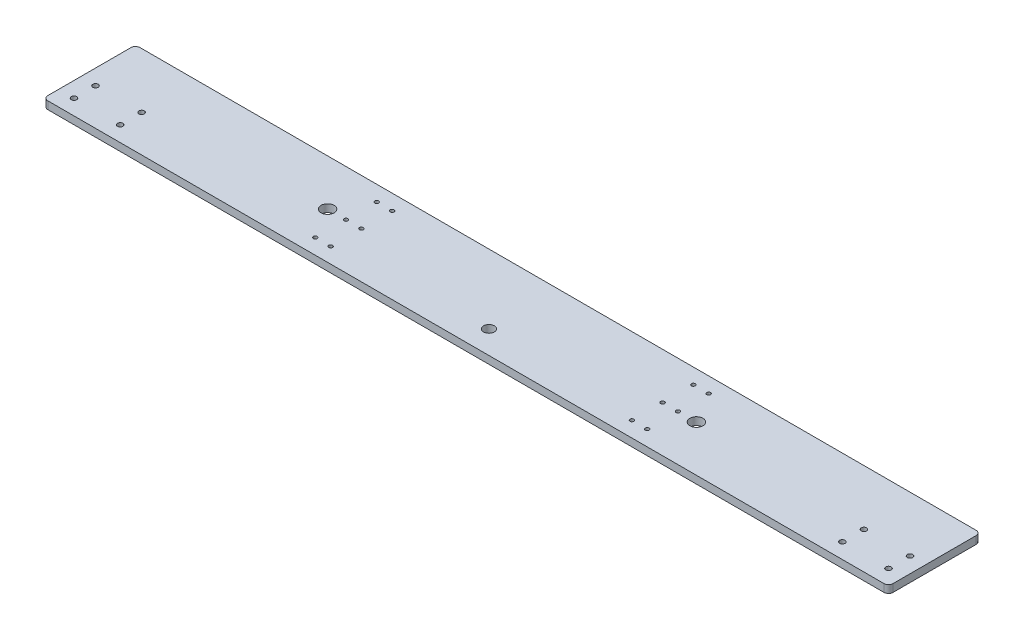
SolidWorks part; units mm, degrees
ref_plane "Front" through (0, 0, 0) normal (0, 0, 1) x (1, 0, 0)
ref_plane "Top" through (0, 0, 0) normal (0, 1, 0) x (1, 0, 0)
ref_plane "Right" through (0, 0, 0) normal (1, 0, 0) x (0, 0, -1)
sketch "草图1" plane through (0, 0, 0) normal (0, 1, 0) x (1, 0, 0)
  line L1 (-275, -30) -> (275, -30)
  line L2 (-275, -30) -> (-275, 30)
  line L3 (-275, 30) -> (275, 30)
  line L4 (275, -30) -> (275, 30)
  line L5 (-275, -30) -> (275, 30) construction
  line L6 (-275, 30) -> (275, -30) construction
  point P0 (0, 0)
  dimension "D1" = 550
  dimension "D2" = 60
extrude "凸台-拉伸1" add sketch "草图1" against normal blind 5 contours L3 L4 L1 L2
sketch "草图2" plane through (0, 0, 0) normal (0, 1, 0) x (1, 0, 0)
  line L0 (-275, -30) -> (275, -30) construction
  circle A0 centre (0, -15) radius 3.5
  dimension "D1" = 7
  dimension "D2" = 15
extrude "切除-拉伸2" cut sketch "草图2" against normal through all contours A0
sketch "草图4" plane through (0, 0, 0) normal (0, 1, 0) x (1, 0, 0)
  line L0 (-275, -30) -> (275, -30) construction
  circle A0 centre (-98, -20) radius 1
  circle A1 centre (0, -15) radius 2.65 construction
  dimension "D1" = 98
  dimension "D2" = 10
  dimension "D3" = 2
extrude "切除-拉伸4" cut sketch "草图4" against normal through all contours A0
pattern_linear "阵列(线性)2" count 3 spacing 20 along (0, 0, -1) count 2 spacing 10 along (-1, 0, 0) of "切除-拉伸4"
mirror "镜向1" about plane through (0, 0, 0) normal (1, 0, 0) of "阵列(线性)2"
sketch "草图6" plane through (0, 0, 0) normal (0, 1, 0) x (1, 0, 0)
  line L0 (-275, 0) -> (-130.6748, 0) construction
  line L1 (-275, -30) -> (-275, 30) construction
  line L2 (-275, -30) -> (275, -30) construction
  circle A0 centre (-265, -20) radius 1.75
  dimension "D3" = 3.5
  dimension "D1" = 10
  dimension "D2" = 10
extrude "切除-拉伸5" cut sketch "草图6" against normal through all contours A0
pattern_linear "阵列(线性)3" count 2 spacing 14 along (0, 0, -1) count 2 spacing 30 along (1, 0, 0) of "切除-拉伸5"
mirror "镜向2" about plane through (0, 0, 0) normal (1, 0, 0) of "阵列(线性)3"
sketch "草图7" plane through (0, 0, 0) normal (0, 1, 0) x (1, 0, 0)
  circle A0 centre (-120, 0) radius 4.25
  dimension "D1" = 8.5
  dimension "D2" = 120
extrude "切除-拉伸6" cut sketch "草图7" against normal blind 10
mirror "镜向3" about plane through (0, 0, 0) normal (1, 0, 0) of "切除-拉伸6"
fillet "圆角3" radius 3 1 edges at (-275, -2.5, 30)
fillet "圆角4" radius 3 1 edges at (-275, -2.5, -30)
fillet "圆角5" radius 3 1 edges at (275, -2.5, -30)
fillet "圆角6" radius 3 1 edges at (275, -2.5, 30)
hole_wizard "M3 螺纹孔2" positions "草图10" profile "草图11" tap size "M3" standard "GB" end condition through all
sketch "草图10" plane through (0, 0, 0) normal (0, 1, 0) x (1, 0, 0)
  point P0 (-98, -20)
  point P3 (-98, 0)
  point P6 (-98, 20)
  point P9 (-108, 20)
  point P12 (-108, 0)
  point P15 (-108, -20)
  point P18 (98, -20)
  point P21 (108, -20)
  point P24 (98, 0)
  point P27 (108, 0)
  point P30 (108, 20)
  point P33 (98, 20)
sketch "草图11" plane through (-98, 0, 20) normal (1, 0, 0) x (0, 0, 1)
  line L0 (0, 0) -> (0, 5)
  line L1 (0, 5) -> (1.25, 5)
  line L2 (1.25, 5) -> (1.25, 0)
  line L5 (1.25, 0) -> (0, 0)
  line L11 (0, -6.35) -> (0, 107.95) construction
  dimension "通孔螺纹孔钻头直径" = 2.5
  dimension "通孔螺纹孔钻头深度" = 5
cosmetic thread "孔螺蚊线1" parameters "D2"=3
cosmetic thread "孔螺蚊线2" parameters "D2"=3
cosmetic thread "孔螺蚊线3" parameters "D2"=3
cosmetic thread "孔螺蚊线4" parameters "D2"=3
cosmetic thread "孔螺蚊线5" parameters "D2"=3
cosmetic thread "孔螺蚊线6" parameters "D2"=3
cosmetic thread "孔螺蚊线7" parameters "D2"=3
cosmetic thread "孔螺蚊线8" parameters "D2"=3
cosmetic thread "孔螺蚊线9" parameters "D2"=3
cosmetic thread "孔螺蚊线10" parameters "D2"=3
cosmetic thread "孔螺蚊线11" parameters "D2"=3
cosmetic thread "孔螺蚊线12" parameters "D2"=3
